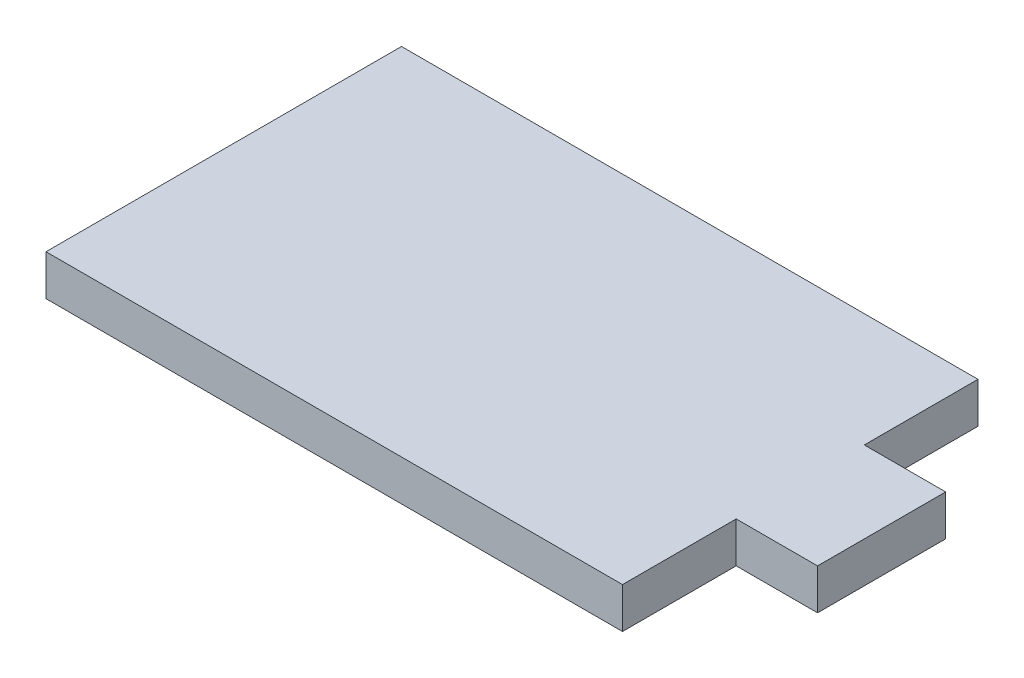
SolidWorks part; units mm, degrees
ref_plane "Front Plane" through (0, 0, 0) normal (0, 0, 1) x (1, 0, 0)
ref_plane "Top Plane" through (0, 0, 0) normal (0, 1, 0) x (1, 0, 0)
ref_plane "Right Plane" through (0, 0, 0) normal (1, 0, 0) x (0, 0, -1)
sketch "Sketch1" plane through (0, 0, 0) normal (0, 1, 0) x (1, 0, 0)
  line L0 (-22.5, 8.875) -> (22.5, 8.875)
  line L1 (22.5, 8.875) -> (22.5, 0)
  line L2 (22.5, 0) -> (28.85, 0)
  line L3 (28.85, 0) -> (28.85, -10)
  line L4 (28.85, -10) -> (22.5, -10)
  line L5 (22.5, -10) -> (22.5, -18.875)
  line L6 (22.5, -18.875) -> (-22.5, -18.875)
  line L7 (-22.5, -18.875) -> (-22.5, -10)
  line L8 (-22.5, -10) -> (-28.85, -10)
  line L9 (-28.85, -10) -> (-28.85, 0)
  line L10 (-28.85, 0) -> (-22.5, 0)
  line L11 (-22.5, 0) -> (-22.5, 8.875)
  line L12 (-22.5, 0) -> (-22.5, -10) construction
  point P11 (0, 8.875)
  point P14 (-28.85, -5)
  dimension "D1" = 6.35
  dimension "D2" = 10
  dimension "D3" = 45
  dimension "D4" = 27.75
extrude "Boss-Extrude1" add sketch "Sketch1" along normal blind 3.175 contours L11 L12 L7 L6 L5 L4 L3 L2 L1 L0 region at (1.2424, 0, 5)
equation "\"length\"= 27.75mm"
equation "\"w_mach\"= 45mm"
equation "\"w_tab\"= 10mm"
equation "\"t_wood\"= 0.125in"
equation "\"t_side\"= 0.25in"
equation "\"D1@Sketch1\"=\"t_side\""
equation "\"D2@Sketch1\"=\"w_tab\""
equation "\"D3@Sketch1\"=\"w_mach\""
equation "\"D4@Sketch1\"=\"length\""
equation "\"D1@Boss-Extrude1\"=\"t_wood\""
